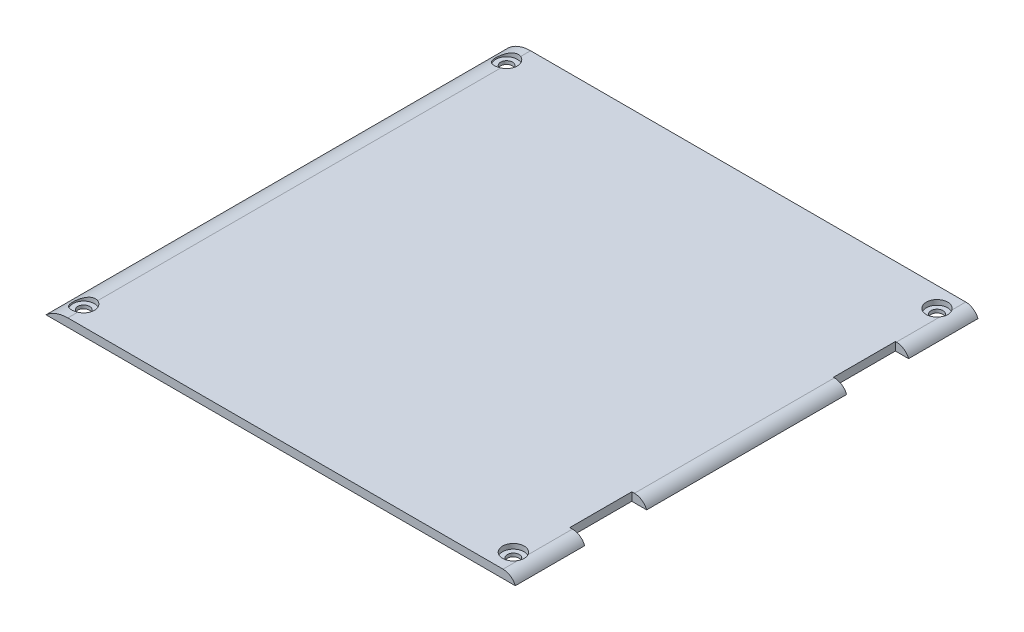
SolidWorks part; units mm, degrees
ref_plane "Front Plane" through (0, 0, 0) normal (0, 0, 1) x (1, 0, 0)
ref_plane "Top Plane" through (0, 0, 0) normal (0, 1, 0) x (1, 0, 0)
ref_plane "Right Plane" through (0, 0, 0) normal (1, 0, 0) x (0, 0, -1)
sketch "Sketch1" plane through (0, 0, 0) normal (0, 1, 0) x (1, 0, 0)
  line L1 (-71, 70) -> (71, 70)
  line L2 (-71, 70) -> (-71, -70)
  line L3 (-71, -70) -> (71, -70)
  line L4 (71, 70) -> (71, -70)
  line L5 (-71, 70) -> (71, -70) construction
  line L6 (-71, -70) -> (71, 70) construction
  point P0 (0, 0)
  dimension "D1" = 140
  dimension "D2" = 142
extrude "Boss-Extrude1" add sketch "Sketch1" against normal blind 2.5
sketch "Sketch5" plane through (71, 0, 0) normal (1, 0, 0) x (0, 0, -1)
  line L0 (-70, -2.5) -> (-70, 0) construction
  line L1 (-70, 0) -> (70, 0) construction
  point P0 (-70, -1.25)
  point P1 (-49, 0)
  point P4 (49, 0)
  point P7 (70, 0)
  point P8 (-30.25, 0)
  point P10 (30.25, 0)
  dimension "D1" = 21
  dimension "D2" = 21
  dimension "D3" = 18.75
  dimension "D4" = 18.75
sketch "Sketch6" plane through (0, 0, 0) normal (0, 1, 0) x (1, 0, 0)
  line L1 (67, 49) -> (71, 49)
  line L2 (67, 49) -> (67, 30.25)
  line L3 (67, 30.25) -> (71, 30.25)
  line L4 (71, 49) -> (71, 30.25)
  point P0 (67, 49)
  point P1 (66.5, 30.25)
  point P2 (67, -30.25)
  point P3 (67, -49)
  dimension "D1" = 4
  dimension "D2" = 4.5
  dimension "D3" = 4
  dimension "D4" = 4
extrude "Cut-Extrude1" cut sketch "Sketch6" against normal through all
sketch "Sketch7" plane through (0, 0, 0) normal (0, 1, 0) x (1, 0, 0)
  line L1 (71, -30.25) -> (66.5, -30.25)
  line L2 (71, -30.25) -> (71, -49)
  line L3 (71, -49) -> (66.5, -49)
  line L4 (66.5, -30.25) -> (66.5, -49)
extrude "Cut-Extrude2" cut sketch "Sketch7" against normal through all contours L4 L3 L2 L1
sketch "Sketch8" plane through (0, 0, 0) normal (0, 1, 0) x (1, 0, 0)
  point P0 (-65.6358, 64)
  point P1 (64.5958, 64)
  point P2 (64.4148, -64)
  point P3 (-65.5958, -64)
  point P4 (0, 0)
  point P5 (0, 0)
  point P6 (0, 0)
  point P7 (0, 0)
  point P8 (0, 0)
  point P9 (0, 0)
  point P10 (0, 0)
  point P11 (0, 0)
  point P12 (0, 0)
  point P13 (0, 0)
  point P14 (0, 0)
  point P15 (0, 0)
  point P16 (0, 0)
  point P17 (0, 0)
  point P18 (0, 0)
  point P19 (0, 0)
  point P20 (0, 0)
  point P21 (0, 0)
  point P22 (0, 0)
  point P23 (0, 0)
  point P24 (0, 0)
  point P25 (0, 0)
  point P26 (0, 0)
  point P27 (0, 0)
  point P28 (0, 0)
  point P29 (0, 0)
  point P30 (0, 0)
  point P31 (0, 0)
  point P32 (0, 0)
  point P33 (0, 0)
  point P34 (0, 0)
  point P35 (0, 0)
hole_wizard "CBORE for M3 Cheese Head Screw1" positions "3DSketch1" profile "Sketch9" counterbore size "M3" standard "AS" end condition through all
sketch3d "3DSketch1"
  point P0 (-65.6358, 0, -64)
  point P3 (64.5958, 0, -64)
  point P6 (64.4148, 0, 64)
  point P9 (-65.5958, 0, 64)
sketch "Sketch9" plane through (-65.6358, 0, -64) normal (1, 0, 0) x (0, 0, 1)
  line L0 (0, 0) -> (0, 2.5)
  line L1 (0, 2.5) -> (1.8, 2.5)
  line L3 (1.8, 2.5) -> (1.8, 1.5)
  line L4 (1.8, 1.5) -> (3.25, 1.5)
  line L5 (3.25, 1.5) -> (3.25, 0)
  line L7 (3.25, 0) -> (0, 0)
  line L11 (0, -6.35) -> (0, 107.95) construction
  dimension "Thru Hole Dia." = 3.6
  dimension "Thru Hole Depth" = 2.5
  dimension "C'Bore Dia." = 6.5
  dimension "C'Bore Depth" = 1.5
fillet "Fillet4" radius 10 1 edges at (-71, 0, 0)
fillet "Fillet7" radius 4 3 edges at (71, 0, 59.5) (71, 0, 0) (71, 0, -59.5)
